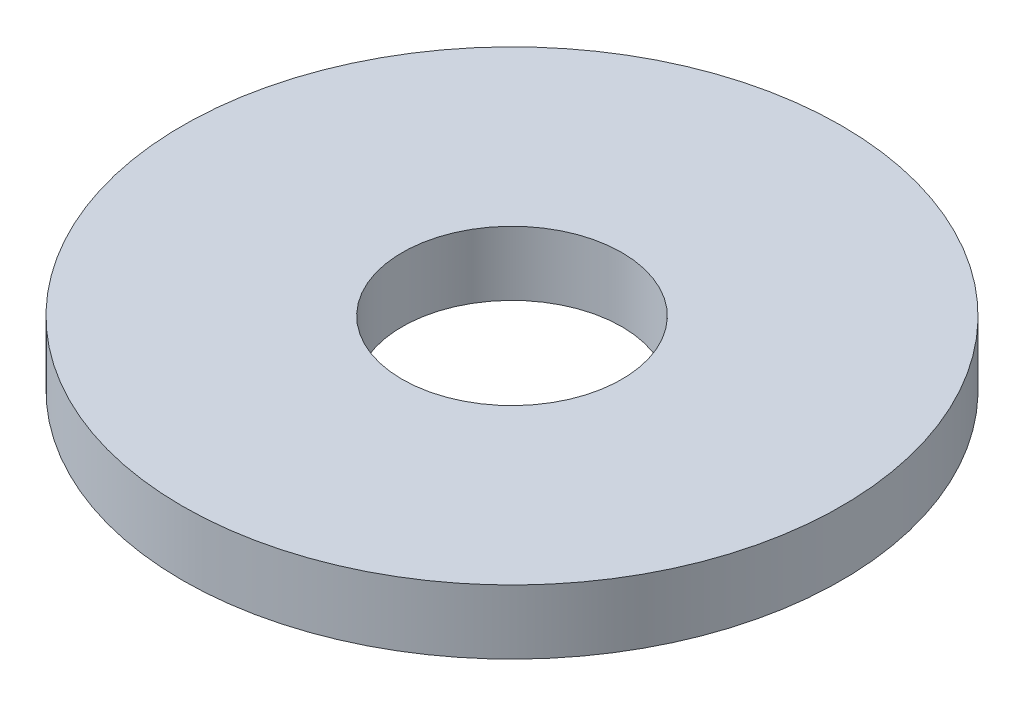
SolidWorks part; units mm, degrees
ref_plane "Front Plane" through (0, 0, 0) normal (0, 0, 1) x (1, 0, 0)
ref_plane "Top Plane" through (0, 0, 0) normal (0, 1, 0) x (1, 0, 0)
ref_plane "Right Plane" through (0, 0, 0) normal (1, 0, 0) x (0, 0, -1)
sketch "Sketch1" plane through (0, 0, 0) normal (0, 1, 0) x (1, 0, 0)
  circle A0 centre (0, 0) radius 97.5
  dimension "FLANGE_OD" = 195
extrude "Boss-Extrude1" add sketch "Sketch1" along normal blind 19
sketch "Sketch2" plane through (0, 0, 0) normal (0, 1, 0) x (1, 0, 0)
  circle A0 centre (0, 0) radius 32.5
  dimension "BORE_D" = 65
extrude "Cut-Extrude1" cut sketch "Sketch2" along normal through all
sketch "Sketch3" plane through (0, 19, 0) normal (0, 1, 0) x (1, 0, 0)
  circle A0 centre (0, 0) radius 20.0372 construction
  circle A1 centre (-20.0372, 0) radius 3.2384
  dimension "BOLT_D" = 6.4769
  dimension "BOLT_PCD" = 40.0743
extrude "Cut-Extrude2" cut sketch "Sketch3" against normal blind 13.9019 rebuild error yes
pattern_circular "CirPattern1" count 8 over 360 rebuild error yes
